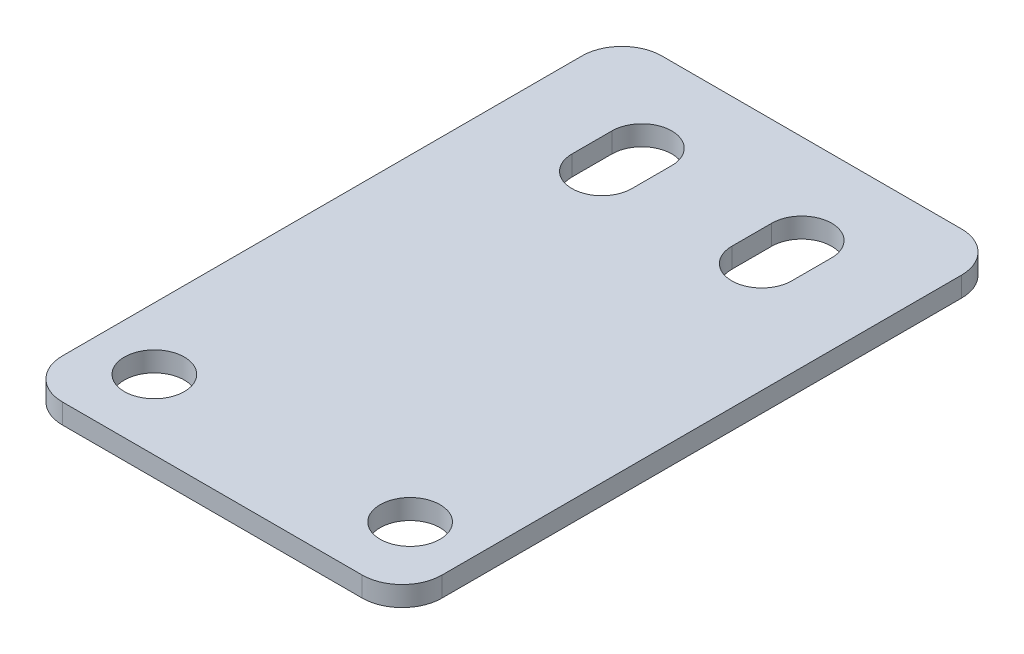
SolidWorks part; units mm, degrees
material "普通碳钢"
ref_plane "前视基准面" through (0, 0, 0) normal (0, 0, 1) x (1, 0, 0)
ref_plane "上视基准面" through (0, 0, 0) normal (0, 1, 0) x (1, 0, 0)
ref_plane "右视基准面" through (0, 0, 0) normal (1, 0, 0) x (0, 0, -1)
sketch "草图1" plane through (0, 0, 0) normal (0, 1, 0) x (1, 0, 0)
  line L0 (-63.3257, 0) -> (68.8834, 0) construction
  line L1 (0, 47.5284) -> (0, -48.1159) construction
  line L2 (-9.5, 26.5) -> (-9.5, -3.5)
  line L3 (-9.5, -3.5) -> (9.5, -3.5)
  line L4 (9.5, -3.5) -> (9.5, 26.5)
  line L5 (9.5, 26.5) -> (-9.5, 26.5)
  line L6 (-4, 22) -> (-4, 20) construction
  line L7 (-2.5, 22) -> (-2.5, 20)
  line L8 (-5.5, 22) -> (-5.5, 20)
  line L9 (4, 22) -> (4, 20) construction
  line L10 (5.5, 22) -> (5.5, 20)
  line L11 (2.5, 22) -> (2.5, 20)
  circle A0 centre (-6.4, 0) radius 1.5
  circle A1 centre (6.4, 0) radius 1.5
  arc A2 (-2.5, 22) -> (-5.5, 22) centre (-4, 22) ccw
  arc A3 (-5.5, 20) -> (-2.5, 20) centre (-4, 20) ccw
  arc A4 (5.5, 22) -> (2.5, 22) centre (4, 22) ccw
  arc A5 (2.5, 20) -> (5.5, 20) centre (4, 20) ccw
  point P15 (-4, 21)
  point P20 (4, 21)
  dimension "D2" = 3
  dimension "D5" = 1.5
  dimension "D1" = 12.8
  dimension "D3" = 19
  dimension "D4" = 3.5
  dimension "D6" = 8
  dimension "D7" = 21
  dimension "D8" = 30
  dimension "D9" = 2
base flange "基体-法兰1" sketch "草图1" thickness 1 reverse thickness direction no parameters "D1"=0
fillet "圆角1" radius 2 4 edges at (-9.5, -0.5, 3.5) (9.5, -0.5, 3.5) (9.5, -0.5, -26.5) (-9.5, -0.5, -26.5)
sketch "折弯-线1" [suppressed] plane through (0, 0, 0) normal (0, 1, 0) x (1, 0, 0)
sketch "边界框1" [suppressed] plane through (0, 0, 0) normal (0, 1, 0) x (1, 0, 0)
sheet metal parameters "钣金6" thickness 1 parameters "D1"=0
flat pattern "平板型式6" [suppressed]
sketch "折弯-线2" plane through (0, 0, 0) normal (0, 1, 0) x (1, 0, 0)
sketch3d "边界框2" [suppressed]
  line L0 (9.5, 26.5, 0) -> (9.5, -3.5, 0) construction
  line L1 (-9.5, 26.5, 0) -> (-9.5, -3.5, 0) construction
  line L2 (9.5, 26.5, 0) -> (-9.5, 26.5, 0) construction
  line L3 (9.5, -3.5, 0) -> (-9.5, -3.5, 0) construction
